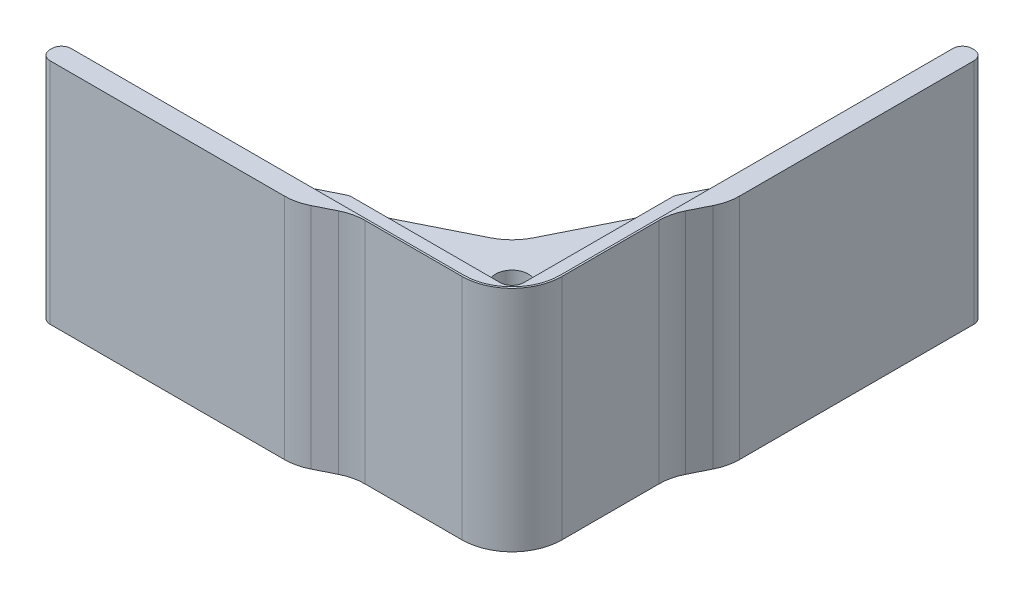
SolidWorks part; units mm, degrees
material "Nylon 101"
ref_plane "Front Plane" through (0, 0, 0) normal (0, 0, 1) x (1, 0, 0)
ref_plane "Top Plane" through (0, 0, 0) normal (0, 1, 0) x (1, 0, 0)
ref_plane "Right Plane" through (0, 0, 0) normal (1, 0, 0) x (0, 0, -1)
sketch "Sketch1" plane through (0, 0, 0) normal (0, 1, 0) x (1, 0, 0)
  line L0 (0, -18.288) -> (-106.3752, -18.288)
  line L1 (18.288, 0) -> (18.288, 106.3752)
  line L2 (-106.3752, -18.288) -> (-106.3752, -12.7)
  line L3 (-106.3752, -12.7) -> (0, -12.7)
  line L4 (12.7, 0) -> (12.7, 106.3752)
  line L5 (12.7, 106.3752) -> (18.288, 106.3752)
  line L6 (-5.6667, 11.3657) -> (-53.935, -12.7)
  line L7 (-11.3657, 5.6667) -> (12.7, 53.935)
  circle A0 centre (0, 0) radius 4.2862
  arc A1 (0, -18.288) -> (18.288, 0) centre (0, 0) ccw
  circle A2 centre (0, 0) radius 12.7
  dimension "D1" = 8.5725
  dimension "D2" = 25.4
  dimension "D4" = 5.588
  dimension "D5" = 106.3752
  dimension "D6" = 26.5
  dimension "D3" = 12.7
extrude "Boss-Extrude1" add sketch "Sketch1" along normal blind 50.8 contours A2 L3 L2 L0 A1 L1 L5 L4 | A2 A0 | A2 L3 | A2 L4 L7 | A2 L6 L7 region at (-53.1876, 0, 16.525) region at (-24.9461, 0, 5.9194) region at (-10.494, 0, 6.4939) region at (5.9194, 0, -24.9461) region at (-9.0813, 0, -9.0813)
fillet "Fillet2" radius 2.54 4 edges at (12.7, 25.4, -106.3752) (18.288, 25.4, -106.3752) (-106.3752, 25.4, 12.7) (-106.3752, 25.4, 18.288)
ref_plane "Plane1" through (0, 25.4, 0) normal (0, 1, 0) x (1, 0, 0)
sketch "Sketch7" plane through (0, 50.8, 0) normal (0, 1, 0) x (1, 0, 0)
  line L1 (4.826, -4.826) -> (-38.1422, -4.826)
  line L2 (4.826, -4.826) -> (4.826, 38.1422)
  line L3 (4.826, 38.1422) -> (-38.1422, 38.1422)
  line L4 (-38.1422, -4.826) -> (-38.1422, 38.1422)
  line L6 (-9.4696, 9.4696) -> (-53.935, -12.7) construction
  arc A0 (-2.7214, -3.9084) -> (3.9084, 2.7214) centre (0, 0) ccw construction
  dimension "D1" = 4.826
  dimension "D2" = 4.826
extrude "Cut-Extrude3" cut sketch "Sketch7" against normal blind 3.429
fillet "Fillet9" radius 3.175 3 edges at (4.826, 49.0855, -38.1422) (4.826, 49.0855, 4.826) (-38.1422, 49.0855, 4.826)
sketch "Sketch8" plane through (0, 25.4, 0) normal (0, 1, 0) x (1, 0, 0)
  line L0 (0, -12.7) -> (-103.8352, -12.7)
  line L10 (12.7, 53.935) -> (5.1596, 38.8112)
  line L11 (4.826, 37.3946) -> (4.826, -1.651)
  line L12 (1.651, -4.826) -> (-37.3946, -4.826)
  line L13 (-38.8112, -5.1596) -> (-53.935, -12.7)
  line L14 (-53.935, -12.7) -> (-103.8352, -12.7)
  line L15 (-106.3752, -15.24) -> (-106.3752, -15.748)
  line L16 (-103.8352, -18.288) -> (0, -18.288)
  line L17 (18.288, 0) -> (18.288, 103.8352)
  line L18 (15.748, 106.3752) -> (15.24, 106.3752)
  line L19 (12.7, 103.8352) -> (12.7, 53.935)
  line L25 (-106.3752, -15.24) -> (-106.3752, -15.748)
  line L26 (-103.8352, -18.288) -> (0, -18.288)
  line L27 (18.288, 0) -> (18.288, 103.8352)
  line L28 (15.748, 106.3752) -> (15.24, 106.3752)
  line L29 (12.7, 103.8352) -> (12.7, 0)
  arc A0 (0, -12.7) -> (12.7, 0) centre (0, 0) ccw
  arc A9 (5.1596, 38.8112) -> (4.826, 37.3946) centre (8.001, 37.3946) ccw
  arc A10 (1.651, -4.826) -> (4.826, -1.651) centre (1.651, -1.651) ccw
  arc A11 (-37.3946, -4.826) -> (-38.8112, -5.1596) centre (-37.3946, -8.001) ccw
  arc A12 (-103.8352, -12.7) -> (-106.3752, -15.24) centre (-103.8352, -15.24) ccw
  arc A13 (-106.3752, -15.748) -> (-103.8352, -18.288) centre (-103.8352, -15.748) ccw
  arc A14 (0, -18.288) -> (18.288, 0) centre (0, 0) ccw
  arc A15 (18.288, 103.8352) -> (15.748, 106.3752) centre (15.748, 103.8352) ccw
  arc A16 (15.24, 106.3752) -> (12.7, 103.8352) centre (15.24, 103.8352) ccw
  arc A21 (-103.8352, -12.7) -> (-106.3752, -15.24) centre (-103.8352, -15.24) ccw
  arc A22 (-106.3752, -15.748) -> (-103.8352, -18.288) centre (-103.8352, -15.748) ccw
  arc A23 (0, -18.288) -> (18.288, 0) centre (0, 0) ccw
  arc A24 (18.288, 103.8352) -> (15.748, 106.3752) centre (15.748, 103.8352) ccw
  arc A25 (15.24, 106.3752) -> (12.7, 103.8352) centre (15.24, 103.8352) ccw
  dimension "D1" = 0
extrude "Boss-Extrude2" add sketch "Sketch8" along normal mid plane 60.325
sketch "Sketch9" plane through (0, 55.5625, 0) normal (0, 1, 0) x (1, 0, 0)
  line L0 (-103.8352, -18.288) -> (0, -18.288) construction
  line L1 (-38.862, -18.288) -> (18.288, -18.288)
  line L2 (-38.862, -18.288) -> (-38.862, -13.208)
  line L3 (-38.862, -13.208) -> (0, -13.208)
  line L4 (18.288, -18.288) -> (18.288, -13.9066)
  line L5 (18.288, 0) -> (18.288, 103.8352) construction
  line L6 (18.288, 38.862) -> (13.208, 38.862)
  line L7 (18.288, 38.862) -> (18.288, -18.288)
  line L8 (18.288, -18.288) -> (13.7882, -18.288)
  line L9 (13.208, 38.862) -> (13.208, 0)
  line L10 (-38.862, -18.288) -> (-28.6731, -13.208)
  line L11 (18.288, 38.862) -> (13.208, 28.6731)
  line L12 (-9.4696, 9.4696) -> (-38.8112, -5.1596) construction
  line L13 (-9.4696, 9.4696) -> (5.1596, 38.8112) construction
  arc A0 (0, -13.208) -> (13.208, 0) centre (0, 0) ccw
  arc A1 (0, -18.288) -> (18.288, 0) centre (0, 0) ccw
  arc A2 (0, -18.288) -> (18.288, 0) centre (0, 0) ccw construction
  line M12 (-103.8352, -18.288) -> (0, -18.288)
  arc M13 (0, -18.288) -> (18.288, 0) centre (0, 0) ccw
  line M14 (18.288, 0) -> (18.288, 103.8352)
  dimension "D2" = 5.08
  dimension "D1" = 57.15
extrude "Cut-Extrude4" cut sketch "Sketch9" against normal through all contours A0 L3 L10 L11 L9 M12 M13 M14 region at (-33.4069, 55.5625, 16.4713)
fillet "Fillet10" radius 12.7 7 edges at (-38.862, 25.4, 18.288) (13.208, 25.4, -28.6731) (18.288, 25.4, -38.862) (-28.6731, 25.4, 13.208) (12.7, 25.4, -53.935) (-53.935, 25.4, 12.7) (-9.4696, 23.6855, -9.4696)
equation "\"D1@Sketch1\"=.3125+0.025"
equation "\"D2@Sketch7\"=\"D1@Sketch7\""
